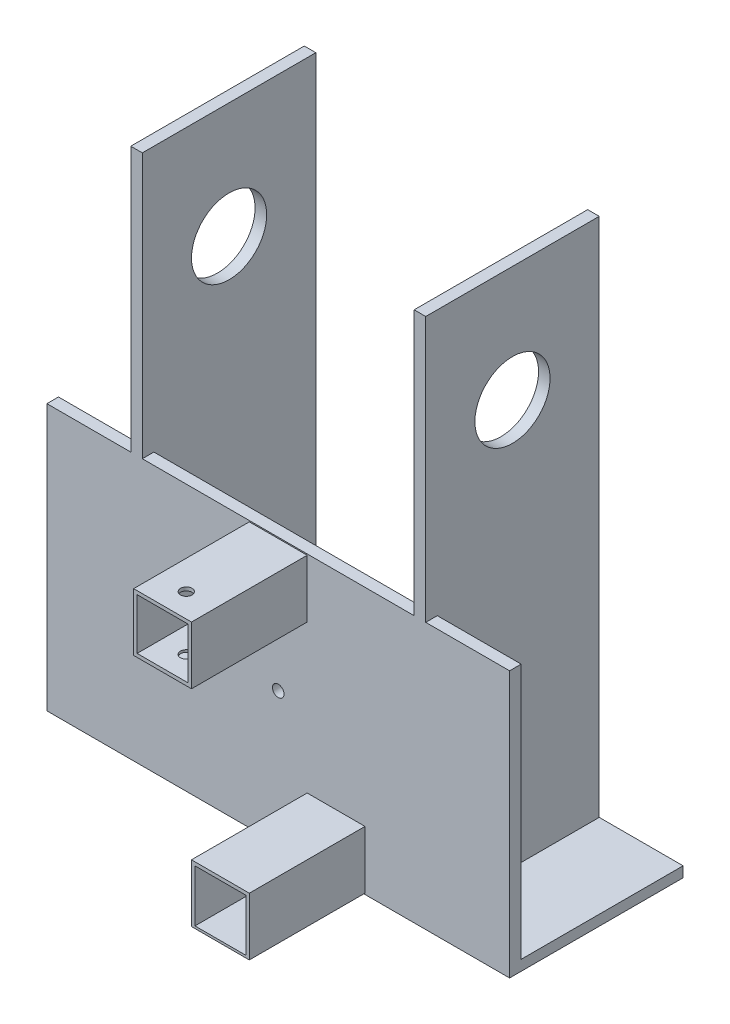
SolidWorks part; units mm, degrees
ref_plane "Plano frontal" through (0, 0, 0) normal (0, 0, 1) x (1, 0, 0)
ref_plane "Plano superior" through (0, 0, 0) normal (0, 1, 0) x (1, 0, 0)
ref_plane "Plano direito" through (0, 0, 0) normal (1, 0, 0) x (0, 0, -1)
sketch "Esboço1" plane through (0, 0, 0) normal (0, 1, 0) x (1, 0, 0)
  line L1 (-200, 75) -> (200, 75)
  line L2 (-200, 75) -> (-200, -75)
  line L3 (-200, -75) -> (200, -75)
  line L4 (200, 75) -> (200, -75)
  line L5 (-200, 75) -> (200, -75) construction
  line L6 (-200, -75) -> (200, 75) construction
  point P0 (0, 0)
  dimension "D1" = 400
  dimension "D2" = 150
extrude "Ressalto-extrusão1" add sketch "Esboço1" along normal blind 9
sketch "Esboço2" plane through (0, 9, 0) normal (0, 1, 0) x (1, 0, 0)
  line L0 (-122.5, 0) -> (122.5, 0) construction
  line L1 (-200, -75) -> (200, -75) construction
  line L2 (-127.5, 75) -> (-117.5, 75)
  line L3 (-127.5, 75) -> (-127.5, -75)
  line L4 (-127.5, -75) -> (-117.5, -75)
  line L5 (-117.5, 75) -> (-117.5, -75)
  line L6 (-127.5, 75) -> (-117.5, -75) construction
  line L7 (-127.5, -75) -> (-117.5, 75) construction
  line L8 (0, 75) -> (0, -75) construction
  line L9 (127.5, -75) -> (117.5, 75) construction
  line L10 (127.5, 75) -> (117.5, -75) construction
  line L11 (117.5, 75) -> (117.5, -75)
  line L12 (127.5, -75) -> (117.5, -75)
  line L13 (127.5, 75) -> (127.5, -75)
  line L14 (127.5, 75) -> (117.5, 75)
  point P4 (0, 0)
  point P14 (0, 0)
  dimension "D1" = 10
  dimension "D2" = 235
  dimension "D3" = 150
extrude "Ressalto-extrusão2" add sketch "Esboço2" along normal blind 450
sketch "Esboço5" plane through (-127.5, 0, 0) normal (-1, 0, 0) x (0, 0, 1)
  line L0 (-75, 459) -> (75, 459) construction
  circle A0 centre (0, 359) radius 32.5
  dimension "D2" = 65
  dimension "D1" = 100
extrude "Corte-extrusão1" cut sketch "Esboço5" against normal blind 300
sketch "Esboço6" plane through (0, 0, 0) normal (0, -1, 0) x (1, 0, 0)
  line L0 (-200, -75) -> (-200, 75) construction
  line L1 (200, 75) -> (-200, 75)
  line L2 (200, 75) -> (200, 65)
  line L3 (200, 65) -> (-200, 65)
  line L4 (-200, 75) -> (-200, 65)
  line L5 (200, 75) -> (-200, 65) construction
  line L6 (200, 65) -> (-200, 75) construction
  point P4 (0, 70)
  dimension "D1" = 10
extrude "Ressalto-extrusão4" add sketch "Esboço6" against normal blind 230
ref_plane "Plano1" through (0, 0, 0) normal (-1, 0, 0) x (0, 0, 1)
sketch "Esboço8" plane through (0, 0, 0) normal (-1, 0, 0) x (0, 0, 1)
  line L0 (75, 0) -> (75, 230) construction
  line L5 (75, 179) -> (175, 179)
  line L6 (75, 179) -> (75, 229)
  line L12 (75, 229) -> (175, 229)
  line L13 (175, 179) -> (175, 229)
  line L14 (75, 230) -> (65, 230) construction
  line L15 (75, 179) -> (175, 229) construction
  line L16 (75, 229) -> (175, 179) construction
  point P4 (125, 204)
  dimension "D1" = 50
  dimension "D2" = 100
  dimension "D3" = 1
extrude "Ressalto-extrusão5" add sketch "Esboço8" against normal mid plane 50
sketch "Esboço9" plane through (0, 230, 0) normal (0, 1, 0) x (-1, 0, 0)
  line L0 (75, 75) -> (-75, 234) construction
  circle A0 centre (0, 154.5) radius 5
  dimension "D1" = 10
extrude "Corte-extrusão3" cut sketch "Esboço9" against normal blind 50
sketch "Esboço7" plane through (0, 0, 65) normal (0, 0, -1) x (-1, 0, 0)
  line L0 (0, 0) -> (0, 230) construction
  line L1 (200, 230) -> (-200, 230) construction
  circle A0 centre (0, 115) radius 5
  dimension "D1" = 10
extrude "Corte-extrusão2" cut sketch "Esboço7" against normal blind 150
ref_plane "Plano2" through (75, 0, 0) normal (-1, 0, 0) x (0, 0, 1)
sketch "Esboço11" plane through (75, 0, 0) normal (-1, 0, 0) x (0, 0, 1)
  line L0 (75, 0) -> (75, 230) construction
  line L1 (75, 51) -> (175, 51)
  line L2 (75, 51) -> (75, 1)
  line L3 (75, 1) -> (175, 1)
  line L4 (175, 51) -> (175, 1)
  line L5 (75, 51) -> (175, 1) construction
  line L6 (75, 1) -> (175, 51) construction
  line L7 (175, 179) -> (175, 229) construction
  line L12 (-75, 0) -> (75, 0) construction
  point P4 (125, 26)
  dimension "D1" = 1
extrude "Ressalto-extrusão6" add sketch "Esboço11" along normal blind 50
sketch "Esboço12" plane through (25, 0, 0) normal (-1, 0, 0) x (0, 0, 1)
  line L0 (175, 1) -> (175, 51) construction
  circle A0 centre (139.8111, 26) radius 5
  point P4 (175, 26)
  dimension "D1" = 10
extrude "Corte-extrusão4" cut sketch "Esboço12" against normal blind 30
sketch "Esboço13" plane through (0, 0, 175) normal (0, 0, 1) x (1, 0, 0)
  line L0 (-25, 229) -> (-25, 179) construction
  line L1 (72, 3) -> (28, 3)
  line L2 (72, 3) -> (72, 48)
  line L3 (72, 48) -> (28, 48)
  line L4 (28, 3) -> (28, 48)
  line L5 (72, 3) -> (28, 48) construction
  line L6 (72, 48) -> (28, 3) construction
  line L7 (22, 226) -> (-22, 226)
  line L8 (22, 226) -> (22, 182)
  line L9 (22, 182) -> (-22, 182)
  line L10 (-22, 226) -> (-22, 182)
  line L11 (22, 226) -> (-22, 182) construction
  line L12 (22, 182) -> (-22, 226) construction
  line L13 (25, 179) -> (-25, 179) construction
  line L14 (25, 229) -> (-25, 229) construction
  line L15 (25, 179) -> (25, 229) construction
  line L16 (25, 1) -> (25, 51) construction
  line L17 (25, 51) -> (75, 51) construction
  line L18 (-200, 0) -> (200, 0) construction
  line L19 (75, 1) -> (75, 51) construction
  point P0 (50, 25.5)
  point P5 (0, 204)
  dimension "D1" = 3
  dimension "D2" = 3
  dimension "D3" = 3
  dimension "D4" = 3
  dimension "D5" = 3
  dimension "D6" = 3
  dimension "D7" = 3
  dimension "D8" = 3
extrude "Corte-extrusão5" cut sketch "Esboço13" against normal up to surface (100 mm away) up to face at (50, 26, 75)
